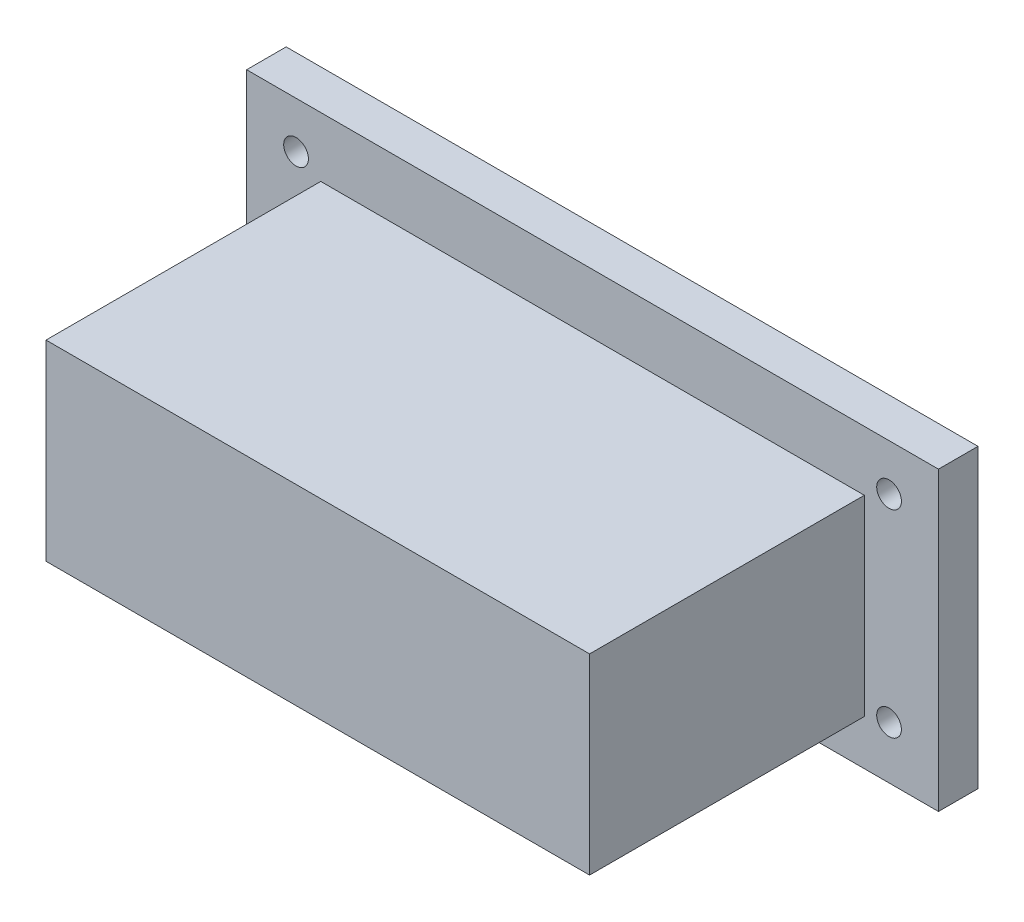
SolidWorks part; units mm, degrees
ref_plane "Front Plane" through (0, 0, 0) normal (0, 0, 1) x (1, 0, 0)
ref_plane "Top Plane" through (0, 0, 0) normal (0, 1, 0) x (1, 0, 0)
ref_plane "Right Plane" through (0, 0, 0) normal (1, 0, 0) x (0, 0, -1)
sketch "Sketch2" plane through (0, 0, 0) normal (0, 0, 1) x (1, 0, 0)
  line L1 (-23.9062, 17.8125) -> (46.0938, 17.8125)
  line L2 (-23.9062, 17.8125) -> (-23.9062, -12.1875)
  line L3 (-23.9062, -12.1875) -> (46.0938, -12.1875)
  line L4 (46.0938, 17.8125) -> (46.0938, -12.1875)
  circle A0 centre (41.0938, 13.125) radius 1.25
  circle A1 centre (41.0938, -6.875) radius 1.25
  circle A2 centre (-18.9062, -6.875) radius 1.25
  circle A3 centre (-18.9062, 13.125) radius 1.25
  dimension "D7" = 2.5
  dimension "D8" = 2.5
  dimension "D9" = 2.5
  dimension "D10" = 2.5
  dimension "D1" = 70
  dimension "D2" = 30
  dimension "D3" = 5
  dimension "D4" = 5
  dimension "D5" = 5
  dimension "D6" = 5
extrude "Boss-Extrude1" add sketch "Sketch2" along normal blind 4
sketch "Sketch4" plane through (0, 0, 4) normal (0, 0, 1) x (1, 0, 0)
  line L0 (-23.9062, 17.8125) -> (-23.9062, -12.1875) construction
  line L5 (46.0938, -12.1875) -> (46.0938, 17.8125) construction
  line L9 (-16.4062, 11.7734) -> (38.5937, 11.7734)
  line L10 (-16.4062, 11.7734) -> (-16.4062, -7.6113)
  line L11 (-16.4062, -7.6113) -> (38.5938, -7.6113)
  line L12 (38.5937, 11.7734) -> (38.5938, -7.6113)
  dimension "D1" = 55
  dimension "D2" = 7.5
  dimension "D3" = 7.5
extrude "Boss-Extrude2" add sketch "Sketch4" along normal blind 27.8
sketch "Sketch6" plane through (-16.4062, 0, 0) normal (-1, 0, 0) x (0, 0, 1)
  line L1 (6.0441, 9.7967) -> (30.1549, 9.7967)
  line L2 (6.0441, 9.7967) -> (6.0441, -5.4471)
  line L3 (6.0441, -5.4471) -> (30.1549, -5.4471)
  line L4 (30.1549, 9.7967) -> (30.1549, -5.4471)
  dimension "D1" = 15.2439
extrude "Cut-Extrude3" cut sketch "Sketch6" against normal blind 54
